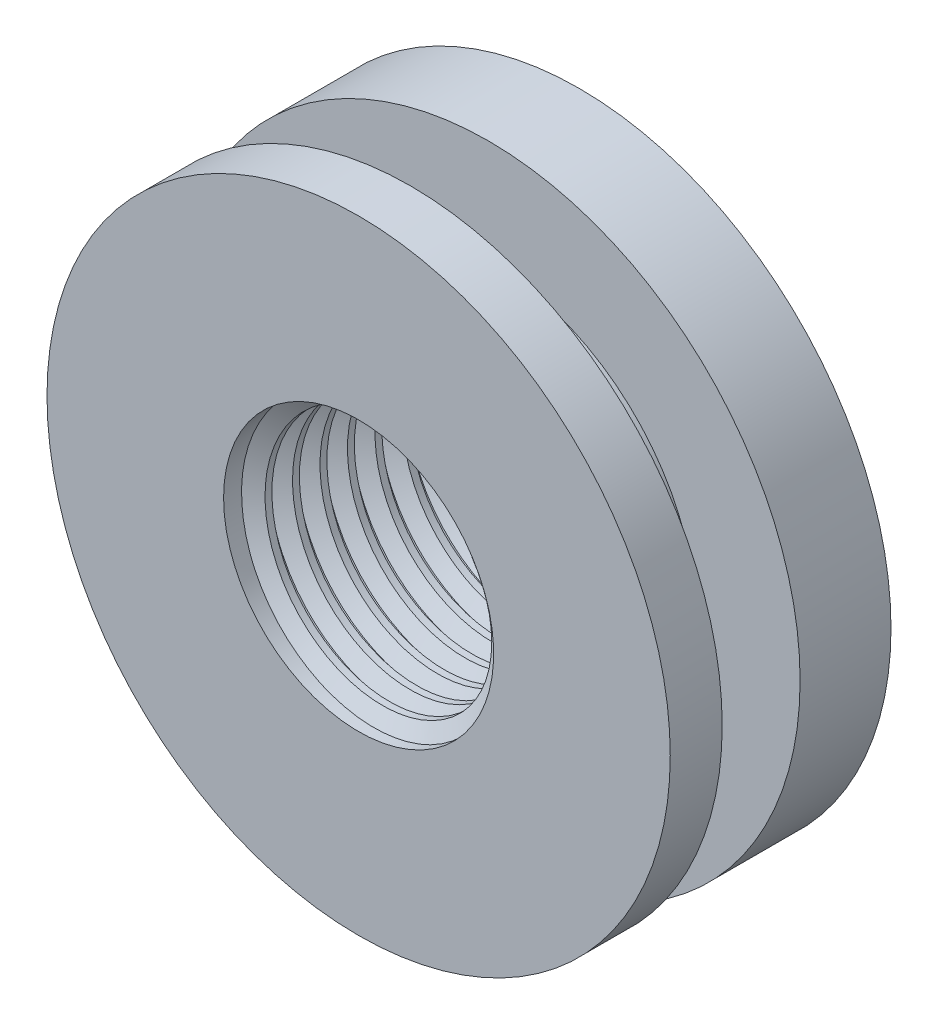
SolidWorks part; units mm, degrees
ref_plane "前视基准面" through (0, 0, 0) normal (0, 0, 1) x (1, 0, 0)
ref_plane "上视基准面" through (0, 0, 0) normal (0, 1, 0) x (1, 0, 0)
ref_plane "右视基准面" through (0, 0, 0) normal (1, 0, 0) x (0, 0, -1)
sketch "草图1" plane through (0, 0, 0) normal (0, 1, 0) x (1, 0, 0)
  line L0 (-11.8347, 0) -> (11.8347, 0) construction
  line L1 (0, 11.8843) -> (0, -11.8843) construction
  line L2 (-5.2, 6.5) -> (-12, 6.5)
  line L3 (-12, 6.5) -> (-12, 3)
  line L4 (-12, 3) -> (-8, 3)
  line L5 (-8, 3) -> (-8, 0)
  line L6 (-8, 0) -> (-12, 0)
  line L7 (-12, 0) -> (-12, -2)
  line L8 (-12, -2) -> (-5.2, -2)
  line L10 (-5.2, 6.5) -> (-5.2, -2)
  point P4 (0, 0)
  point P8 (0, 0)
  dimension "D1" = 2
  dimension "D2" = 3
  dimension "D3" = 12
  dimension "D4" = 8
  dimension "D5" = 3.5
  dimension "D6" = 5.2
revolve "旋转3" add sketch "草图1" angle 360 about L1
thread "螺纹线1" pitch 1.0583 method extrude profile "螺纹线轮廓2" start angle 0, offset 0, length 7.5, pitch 1.0583, diameter 10.4
ref_plane "基准面2" through (5.2, 0, -6.5) normal (0, -1, 0) x (1, 0, 0)
sketch "螺纹线轮廓2" plane through (5.2, 0, -6.5) normal (0, -1, 0) x (1, 0, 0)
  line L0 (0, 0) -> (0, 1.0583) construction
  line L11 (0, 0) -> (0, 0.926)
  line L12 (0, 0.926) -> (-0.5728, 0.5953)
  line L13 (-0.5728, 0.5953) -> (-0.5728, 0.3307)
  line L15 (-0.5728, 0.3307) -> (0, 0)
  line L17 (-0.5728, 0.463) -> (0, 0.463) construction
  point P2 (0, 0)
  dimension "Pitch" = 1.0583
  dimension "Profile_Angle" = 60
  dimension "Profile_Land" = 0.2646
  dimension "Profile_Height" = 0.5728
sketch "草图15" plane through (0, 0, -6.5) normal (0, 0, -1) x (-1, 0, 0)
  circle A0 centre (0, 0) radius 4.3
  dimension "D1" = 8.6
